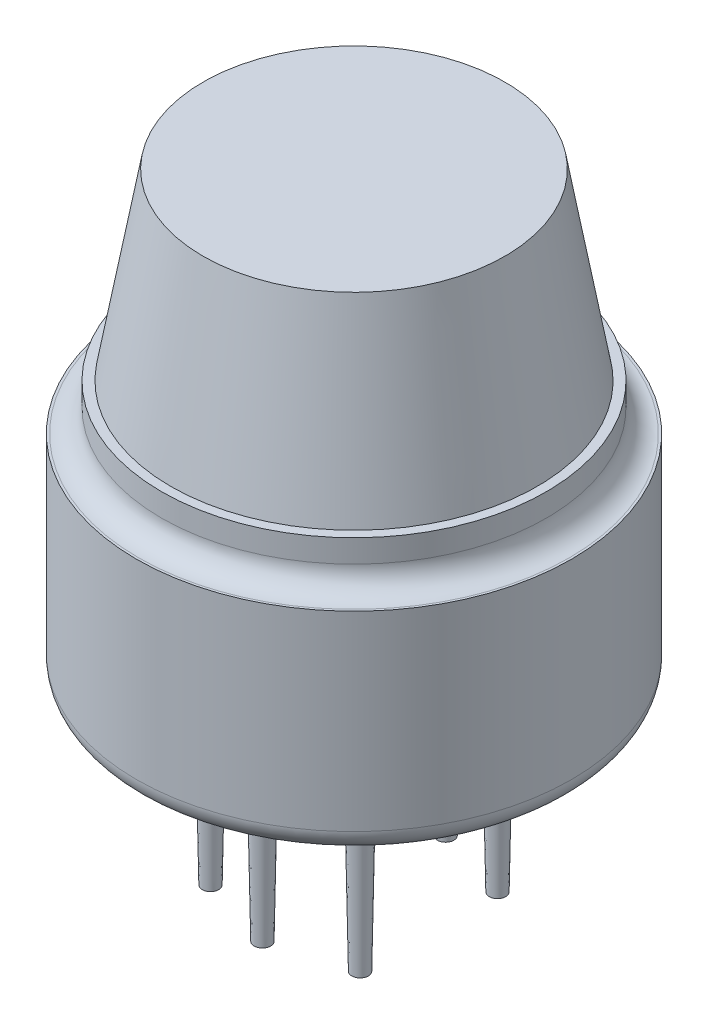
SolidWorks part; units mm, degrees
ref_plane "Front Plane" through (0, 0, 0) normal (0, 0, 1) x (1, 0, 0)
ref_plane "Top Plane" through (0, 0, 0) normal (0, 1, 0) x (1, 0, 0)
ref_plane "Right Plane" through (0, 0, 0) normal (1, 0, 0) x (0, 0, -1)
sketch "Sketch1" plane through (0, 0, 0) normal (0, 1, 0) x (1, 0, 0)
  circle A0 centre (0, 0) radius 9.5
  dimension "D1" = 19
extrude "Boss-Extrude1" add sketch "Sketch1" along normal blind 9.2
sketch "Sketch2" plane through (0, 9.2, 0) normal (0, 1, 0) x (1, 0, 0)
  circle A0 centre (0, 0) radius 8.4
  dimension "D1" = 16.8
extrude "Boss-Extrude2" add sketch "Sketch2" along normal blind 2
sketch "Sketch3" plane through (0, 11.2, 0) normal (0, 1, 0) x (1, 0, 0)
  circle A0 centre (0, 0) radius 8
  dimension "D1" = 16
extrude "Cut-Extrude1" cut sketch "Sketch3" against normal blind 2
fillet "Fillet1" radius 1 1 edges at (0, 9.2, 8.4)
sketch "Sketch4" plane through (0, 11.2, 0) normal (0, 1, 0) x (1, 0, 0)
  circle A0 centre (0, 0) radius 8 construction
  circle A1 centre (0, 0) radius 8
extrude "Boss-Extrude3" add sketch "Sketch4" along normal blind 8 draft 10 separate body
sketch "Sketch5" plane through (0, 0, 0) normal (0, -1, 0) x (1, 0, 0)
  circle A2 centre (0, 0) radius 9
  circle A3 centre (0, 0) radius 9
  dimension "D1" = 0.5
extrude "Cut-Extrude2" cut sketch "Sketch5" against normal blind 0.5
sketch "Sketch6" plane through (0, 0, 0) normal (0, -1, 0) x (-1, 0, 0)
  line L0 (9, 0) -> (-9, 0) construction
  line L1 (0, -9) -> (0, 9) construction
  circle A0 centre (0, 0) radius 9 construction
  circle A1 centre (0, 0) radius 9 construction
  circle A2 centre (3.2655, -3) radius 0.5
  circle A3 centre (-3.2655, -3) radius 0.5
  circle A4 centre (0, -4) radius 0.5
  circle A5 centre (-3.2655, 3) radius 0.5
  circle A6 centre (3.2655, 3) radius 0.5
  circle A7 centre (0, 4) radius 0.5
  dimension "D1" = 1
  dimension "D2" = 3
  dimension "D3" = 1
  dimension "D4" = 3.2655
extrude "Boss-Extrude4" add sketch "Sketch6" along normal blind 8 draft 1 separate body
fillet "Fillet2" radius 1 1 edges at (0, 0, 9.5)
fillet "Fillet3" radius 0.1 1 edges at (0, 0.5, -9)
sketch "Sketch7" plane through (0, 0.5, 0) normal (0, -1, 0) x (1, 0, 0)
  line L0 (-9, 0) -> (9, 0) construction
  circle A0 centre (0, 0) radius 9 construction
  circle A1 centre (0, 0) radius 9 construction
  text T0 "WINSEN" font "Century Gothic" height in points 7
extrude "Cut-Extrude3" cut sketch "Sketch7" against normal blind 0.5
